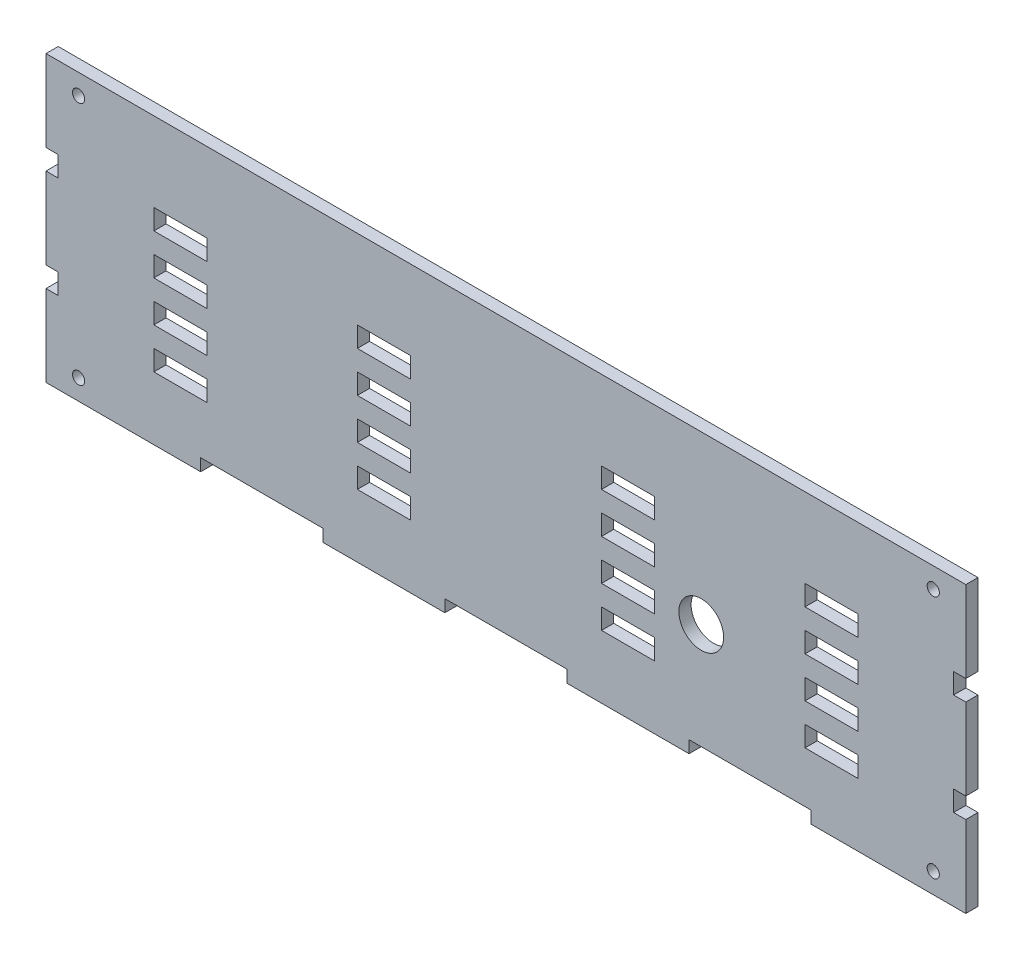
SolidWorks part; units mm, degrees
ref_plane "Front Plane" through (0, 0, 0) normal (0, 0, 1) x (1, 0, 0)
ref_plane "Top Plane" through (0, 0, 0) normal (0, 1, 0) x (1, 0, 0)
ref_plane "Right Plane" through (0, 0, 0) normal (1, 0, 0) x (0, 0, -1)
sketch "Sketch1" plane through (0, 0, 0) normal (0, 0, 1) x (1, 0, 0)
  line L1 (0, 0) -> (220, 0)
  line L2 (0, 0) -> (0, 70)
  line L3 (0, 70) -> (220, 70)
  line L4 (220, 0) -> (220, 70)
  dimension "D1" = 220
  dimension "D2" = 70
extrude "Boss-Extrude1" add sketch "Sketch1" along normal blind 3
sketch "Sketch2" plane through (0, 0, 3) normal (0, 0, 1) x (1, 0, 0)
  line L0 (110, 70) -> (110, 0) construction
  line L1 (220, 70) -> (0, 70) construction
  line L2 (0, 0) -> (220, 0) construction
  line L4 (0, 44) -> (220, 44) construction
  line L5 (5, 5) -> (215, 5) construction
  line L6 (5, 5) -> (5, 65) construction
  line L7 (5, 65) -> (215, 65) construction
  line L8 (215, 5) -> (215, 65) construction
  line L9 (5, 5) -> (215, 65) construction
  line L10 (5, 65) -> (215, 5) construction
  circle A0 centre (5, 65) radius 1.5
  circle A1 centre (215, 65) radius 1.5
  circle A2 centre (215, 5) radius 1.5
  circle A3 centre (5, 5) radius 1.5
  text T0 "RIVO Control" font "Century Schoolbook" height in points 50
  point P9 (110, 44)
  point P10 (110, 35)
  dimension "D5" = 3
  dimension "D1" = 220
  dimension "D2" = 26
  dimension "D3" = 210
  dimension "D4" = 60
extrude "Cut-Extrude1" [suppressed] cut sketch "Sketch2" against normal blind 1
extrude "Cut-Extrude2" cut sketch "Sketch2<2>" against normal through all contours A0 | A3 | A2 | A1 region at (5, 65, 3) region at (215, 65, 3) region at (215, 5, 3) region at (5, 5, 3)
sketch "Sketch2<2>" plane through (0, 0, 3) normal (0, 0, 1) x (1, 0, 0) same geometry as "Sketch2"
sketch "Sketch3" plane through (0, 0, 3) normal (0, 0, 1) x (1, 0, 0)
  line L0 (0, 35) -> (220, 35) construction
  line L1 (0, 70) -> (0, 0) construction
  line L2 (220, 0) -> (220, 70) construction
  line L3 (-3, 45) -> (0, 25) construction
  line L4 (0, 25) -> (-3, 25)
  line L5 (0, 25) -> (0, 45)
  line L6 (0, 45) -> (-3, 45)
  line L7 (-3, 25) -> (-3, 45)
  line L8 (0, 45) -> (-3, 25) construction
  line L9 (0, 35) -> (-3, 35) construction
  line L10 (-3, 70) -> (0, 50) construction
  line L11 (0, 70) -> (-3, 50) construction
  line L12 (0, 70) -> (-3, 70)
  line L13 (-3, 50) -> (-3, 70)
  line L14 (0, 60) -> (-3, 60) construction
  line L15 (0, 50) -> (-3, 50)
  line L16 (-3, 20) -> (0, 0) construction
  line L17 (0, 20) -> (-3, 0) construction
  line L18 (0, 20) -> (-3, 20)
  line L19 (-3, 0) -> (-3, 20)
  line L20 (0, 10) -> (-3, 10) construction
  line L21 (0, 0) -> (-3, 0)
  line L22 (110, 0) -> (110, 70) construction
  line L23 (0, 0) -> (220, 0) construction
  line L24 (220, 70) -> (0, 70) construction
  line L25 (220, 10) -> (223, 10) construction
  line L26 (220, 20) -> (223, 0) construction
  line L27 (223, 20) -> (220, 0) construction
  line L28 (220, 60) -> (223, 60) construction
  line L29 (220, 70) -> (223, 50) construction
  line L30 (223, 70) -> (220, 50) construction
  line L31 (220, 35) -> (223, 35) construction
  line L32 (220, 45) -> (223, 25) construction
  line L33 (223, 45) -> (220, 25) construction
  line L34 (220, 0) -> (223, 0)
  line L35 (223, 0) -> (223, 20)
  line L36 (220, 20) -> (223, 20)
  line L37 (220, 50) -> (223, 50)
  line L38 (223, 50) -> (223, 70)
  line L39 (220, 70) -> (223, 70)
  line L40 (223, 25) -> (223, 45)
  line L41 (220, 45) -> (223, 45)
  line L42 (220, 25) -> (220, 45)
  line L43 (220, 25) -> (223, 25)
  line L44 (0, 70) -> (0, 0)
  line L45 (220, 0) -> (220, 70)
  point P10 (-1.5, 35)
  dimension "D1" = 20
  dimension "D2" = 3
  dimension "D3" = 2
  dimension "D4" = 2
extrude "Boss-Extrude4" add sketch "Sketch3" against normal up to surface (3 mm away) contours L7 L4 L5 L6 | L42 L43 L40 L41 region at (-1.5, 35, 3) region at (221.5, 35, 3) up to face at (216.5, 65, 0)
pattern_linear "LPattern1" count 2 spacing 25 along (0, 1, 0) count 2 spacing 25 along (0, -1, 0) of "Boss-Extrude4"
sketch "Sketch4" plane through (0, 0, 0) normal (0, 0, -1) x (-1, 0, 0)
  line L0 (-155, 0) -> (-185, 0) construction
  line L1 (-185, 0) -> (-185, 3) construction
  line L2 (-185, 3) -> (-155, 3) construction
  line L3 (-155, 3) -> (-155, 0) construction
  line L4 (-95, 0) -> (-125, 0) construction
  line L5 (-125, 0) -> (-125, 3) construction
  line L6 (-125, 3) -> (-95, 3) construction
  line L7 (-95, 3) -> (-95, 0) construction
  line L8 (-35, 0) -> (-65, 0) construction
  line L9 (-65, 0) -> (-65, 3) construction
  line L10 (-65, 3) -> (-35, 3) construction
  line L11 (-35, 3) -> (-35, 0) construction
  line L12 (-155, 0) -> (-185, 0)
  line L13 (-185, 0) -> (-185, 3)
  line L14 (-185, 3) -> (-155, 3)
  line L15 (-155, 3) -> (-155, 0)
  line L16 (-95, 0) -> (-125, 0)
  line L17 (-125, 0) -> (-125, 3)
  line L18 (-125, 3) -> (-95, 3)
  line L19 (-95, 3) -> (-95, 0)
  line L20 (-35, 0) -> (-65, 0)
  line L21 (-65, 0) -> (-65, 3)
  line L22 (-65, 3) -> (-35, 3)
  line L23 (-35, 3) -> (-35, 0)
extrude "Cut-Extrude3" cut sketch "Sketch4" against normal through all
sketch "Sketch5" plane through (0, 0, 3) normal (0, 0, 1) x (1, 0, 0)
  line L0 (158, 43.0279) -> (158, 3) construction
  line L2 (155, 3) -> (185, 3) construction
  line L3 (223, 0) -> (223, 20) construction
  circle A0 centre (158, 29) radius 5.5
  dimension "D1" = 11
  dimension "D2" = 26
  dimension "D3" = 65
extrude "Cut-Extrude4" cut sketch "Sketch5" against normal through all
sketch "Sketch6" plane through (0, 0, 0) normal (0, 0, -1) x (-1, 0, 0)
  line L0 (-140, 0) -> (-140, 70) construction
  line L1 (-125, 0) -> (-155, 0) construction
  line L2 (-223, 70) -> (3, 70) construction
  line L3 (-146.5, 50.5) -> (-133.5, 45.5) construction
  line L4 (-146.5, 45.5) -> (-133.5, 45.5)
  line L5 (-146.5, 45.5) -> (-146.5, 50.5)
  line L6 (-146.5, 50.5) -> (-133.5, 50.5)
  line L7 (-133.5, 45.5) -> (-133.5, 50.5)
  line L8 (-133.5, 50.5) -> (-146.5, 45.5) construction
  line L9 (-196.5, 45.5) -> (-196.5, 50.5)
  line L10 (-196.5, 45.5) -> (-183.5, 45.5)
  line L11 (-183.5, 45.5) -> (-183.5, 50.5)
  line L12 (-196.5, 50.5) -> (-183.5, 50.5)
  line L13 (-196.5, 35.5) -> (-196.5, 40.5)
  line L14 (-196.5, 35.5) -> (-183.5, 35.5)
  line L15 (-183.5, 35.5) -> (-183.5, 40.5)
  line L16 (-196.5, 40.5) -> (-183.5, 40.5)
  line L17 (-196.5, 25.5) -> (-196.5, 30.5)
  line L18 (-196.5, 25.5) -> (-183.5, 25.5)
  line L19 (-183.5, 25.5) -> (-183.5, 30.5)
  line L20 (-196.5, 30.5) -> (-183.5, 30.5)
  line L21 (-196.5, 15.5) -> (-196.5, 20.5)
  line L22 (-196.5, 15.5) -> (-183.5, 15.5)
  line L23 (-183.5, 15.5) -> (-183.5, 20.5)
  line L24 (-196.5, 20.5) -> (-183.5, 20.5)
  line L25 (-146.5, 35.5) -> (-146.5, 40.5)
  line L26 (-146.5, 35.5) -> (-133.5, 35.5)
  line L27 (-133.5, 35.5) -> (-133.5, 40.5)
  line L28 (-146.5, 40.5) -> (-133.5, 40.5)
  line L29 (-146.5, 25.5) -> (-146.5, 30.5)
  line L30 (-146.5, 25.5) -> (-133.5, 25.5)
  line L31 (-133.5, 25.5) -> (-133.5, 30.5)
  line L32 (-146.5, 30.5) -> (-133.5, 30.5)
  line L33 (-146.5, 15.5) -> (-146.5, 20.5)
  line L34 (-146.5, 15.5) -> (-133.5, 15.5)
  line L35 (-133.5, 15.5) -> (-133.5, 20.5)
  line L36 (-146.5, 20.5) -> (-133.5, 20.5)
  line L37 (-110, 70) -> (-110, 3) construction
  line L38 (-95, 3) -> (-125, 3) construction
  line L39 (-86.5, 50.5) -> (-73.5, 45.5) construction
  line L40 (-73.5, 50.5) -> (-86.5, 45.5) construction
  line L41 (-80, 0) -> (-80, 70) construction
  line L42 (-73.5, 20.5) -> (-86.5, 20.5)
  line L43 (-86.5, 15.5) -> (-86.5, 20.5)
  line L44 (-73.5, 15.5) -> (-86.5, 15.5)
  line L45 (-73.5, 15.5) -> (-73.5, 20.5)
  line L46 (-73.5, 30.5) -> (-86.5, 30.5)
  line L47 (-86.5, 25.5) -> (-86.5, 30.5)
  line L48 (-73.5, 25.5) -> (-86.5, 25.5)
  line L49 (-73.5, 25.5) -> (-73.5, 30.5)
  line L50 (-73.5, 40.5) -> (-86.5, 40.5)
  line L51 (-86.5, 35.5) -> (-86.5, 40.5)
  line L52 (-73.5, 35.5) -> (-86.5, 35.5)
  line L53 (-73.5, 35.5) -> (-73.5, 40.5)
  line L54 (-23.5, 20.5) -> (-36.5, 20.5)
  line L55 (-36.5, 15.5) -> (-36.5, 20.5)
  line L56 (-23.5, 15.5) -> (-36.5, 15.5)
  line L57 (-23.5, 15.5) -> (-23.5, 20.5)
  line L58 (-23.5, 30.5) -> (-36.5, 30.5)
  line L59 (-36.5, 25.5) -> (-36.5, 30.5)
  line L60 (-23.5, 25.5) -> (-36.5, 25.5)
  line L61 (-23.5, 25.5) -> (-23.5, 30.5)
  line L62 (-23.5, 40.5) -> (-36.5, 40.5)
  line L63 (-36.5, 35.5) -> (-36.5, 40.5)
  line L64 (-23.5, 35.5) -> (-36.5, 35.5)
  line L65 (-23.5, 35.5) -> (-23.5, 40.5)
  line L66 (-23.5, 50.5) -> (-36.5, 50.5)
  line L67 (-36.5, 45.5) -> (-36.5, 50.5)
  line L68 (-23.5, 45.5) -> (-36.5, 45.5)
  line L69 (-23.5, 45.5) -> (-23.5, 50.5)
  line L70 (-86.5, 45.5) -> (-86.5, 50.5)
  line L71 (-73.5, 50.5) -> (-86.5, 50.5)
  line L72 (-73.5, 45.5) -> (-73.5, 50.5)
  line L73 (-73.5, 45.5) -> (-86.5, 45.5)
  point P6 (-140, 48)
  point P12 (-140, 48)
  point P78 (-80, 48)
  dimension "D1" = 13
  dimension "D2" = 5
  dimension "D3" = 22
  dimension "D4" = 2
  dimension "D5" = 4
extrude "Cut-Extrude5" cut sketch "Sketch6" against normal through all
